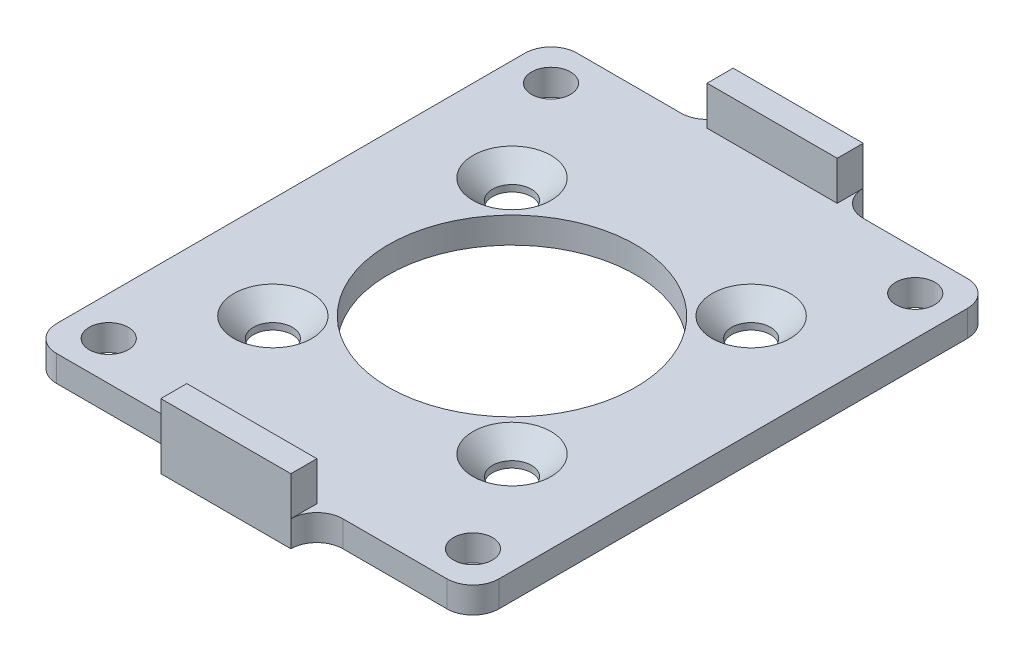
SolidWorks part; units mm, degrees
material "6061-T6 (SS)"
ref_plane "前视基准面" through (0, 0, 0) normal (0, 0, 1) x (1, 0, 0)
ref_plane "上视基准面" through (0, 0, 0) normal (0, 1, 0) x (1, 0, 0)
ref_plane "右视基准面" through (0, 0, 0) normal (1, 0, 0) x (0, 0, -1)
sketch "草图1" plane through (0, 0, 0) normal (0, 1, 0) x (1, 0, 0)
  line L0 (17, 0) -> (17, 40) construction
  line L1 (0, 0) -> (34, 0)
  line L2 (0, 0) -> (0, 40)
  line L3 (0, 40) -> (34, 40)
  line L4 (34, 0) -> (34, 40)
  line L6 (7.8076, 29.1924) -> (26.1924, 29.1924) construction
  line L7 (7.8076, 29.1924) -> (7.8076, 10.8076) construction
  line L8 (7.8076, 10.8076) -> (26.1924, 10.8076) construction
  line L9 (26.1924, 29.1924) -> (26.1924, 10.8076) construction
  line L10 (7.8076, 29.1924) -> (26.1924, 10.8076) construction
  line L11 (7.8076, 10.8076) -> (26.1924, 29.1924) construction
  circle A0 centre (17, 20) radius 9.5
  circle A1 centre (26.1924, 29.1924) radius 1.5
  circle A2 centre (7.8076, 29.1924) radius 1.5
  circle A3 centre (7.8076, 10.8076) radius 1.5
  circle A4 centre (26.1924, 10.8076) radius 1.5
  dimension "D3" = 19
  dimension "D5" = 3
  dimension "D1" = 34
  dimension "D2" = 40
  dimension "D4" = 26
extrude "凸台-拉伸1" add sketch "草图1" along normal blind 2
sketch "草图7" plane through (0, 2, 0) normal (0, 1, 0) x (1, 0, 0)
  circle A0 centre (26.1924, 29.1924) radius 1.5 construction
  circle A1 centre (26.1924, 10.8076) radius 1.5 construction
  circle A2 centre (7.8076, 10.8076) radius 1.5 construction
  circle A3 centre (7.8076, 29.1924) radius 1.5 construction
  circle A4 centre (26.1924, 29.1924) radius 1.5
  circle A5 centre (26.1924, 10.8076) radius 1.5
  circle A6 centre (7.8076, 10.8076) radius 1.5
  circle A7 centre (7.8076, 29.1924) radius 1.5
sketch "草图2" plane through (0, 2, 0) normal (0, 1, 0) x (1, 0, 0)
  line L1 (3, 37) -> (31, 37) construction
  line L2 (3, 37) -> (3, 3) construction
  line L3 (3, 3) -> (31, 3) construction
  line L4 (31, 37) -> (31, 3) construction
  line L5 (3, 37) -> (31, 3) construction
  line L6 (3, 3) -> (31, 37) construction
  point P0 (17, 20)
  dimension "D1" = 28
  dimension "D2" = 34
hole_wizard "Ø3.0 (3) 直径孔1" positions "3D草图1" profile "草图3" hole size "Ø3.0" standard "GB" end condition through all
sketch3d "3D草图1"
  point P0 (3, 2, -37)
  point P3 (31, 2, -37)
  point P6 (31, 2, -3)
  point P9 (3, 2, -3)
sketch "草图3" plane through (3, 2, -37) normal (1, 0, 0) x (0, 0, 1)
  line L0 (0, 0) -> (0, 2)
  line L1 (0, 2) -> (1.5, 2)
  line L2 (1.5, 2) -> (1.5, 0)
  line L5 (1.5, 0) -> (0, 0)
  line L11 (0, -6.35) -> (0, 107.95) construction
  dimension "通孔孔直径" = 3
  dimension "通孔孔深度" = 2
fillet "圆角1" radius 2 4 edges at (0, 1, 0) (34, 1, 0) (34, 1, -40) (0, 1, -40)
sketch "草图5" plane through (0, 0, 0) normal (0, -1, 0) x (1, 0, 0)
  line L0 (17, -20) -> (42.9557, -20) construction
  line L1 (17, -20) -> (17, 3.7236) construction
  line L2 (2, 0) -> (32, 0) construction
  line L3 (12, 0) -> (22, 0)
  line L4 (12, 0) -> (12, 2)
  line L5 (12, 2) -> (22, 2)
  line L6 (22, 0) -> (22, 2)
  line L7 (12, -40) -> (12, -42)
  line L8 (12, -42) -> (22, -42)
  line L9 (22, -40) -> (22, -42)
  line L10 (12, -40) -> (22, -40)
  dimension "D1" = 2
  dimension "D2" = 10
extrude "凸台-拉伸2" add sketch "草图5" against normal blind 5
fillet "圆角2" radius 2 4 edges at (22, 1, -40) (12, 1, -40) (12, 1, 0) (22, 1, 0)
chamfer "倒角1" distance 1.5 angle 45 4 edges at (7.8076, 2, -9.3076) (26.1924, 2, -9.3076) (26.1924, 2, -27.6924) (7.8076, 2, -27.6924)
